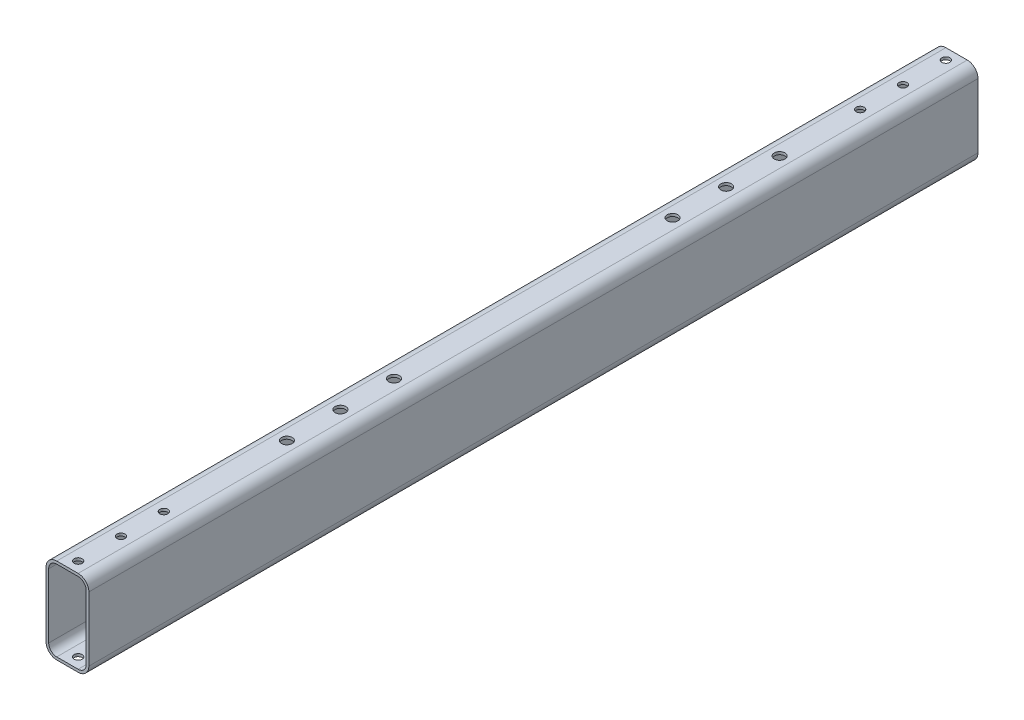
SolidWorks part; units mm, degrees
material "6061-T6 (SS)"
ref_plane "Front Plane" through (0, 0, 0) normal (0, 0, 1) x (1, 0, 0)
ref_plane "Top Plane" through (0, 0, 0) normal (0, 1, 0) x (1, 0, 0)
ref_plane "Right Plane" through (0, 0, 0) normal (1, 0, 0) x (0, 0, -1)
sketch "Sketch1" plane through (0, 0, 0) normal (0, 0, 1) x (1, 0, 0)
  line L1 (-6.35, -25.4) -> (6.35, -25.4)
  line L2 (-12.7, -19.05) -> (-12.7, 19.05)
  line L3 (-6.35, 25.4) -> (6.35, 25.4)
  line L4 (12.7, -19.05) -> (12.7, 19.05)
  line L5 (-12.7, -25.4) -> (12.7, 25.4) construction
  line L6 (-12.7, 25.4) -> (12.7, -25.4) construction
  arc A0 (-12.7, -19.05) -> (-6.35, -25.4) centre (-6.35, -19.05) ccw
  arc A1 (6.35, -25.4) -> (12.7, -19.05) centre (6.35, -19.05) ccw
  arc A2 (6.35, 25.4) -> (12.7, 19.05) centre (6.35, 19.05) cw
  arc A3 (-12.7, 19.05) -> (-6.35, 25.4) centre (-6.35, 19.05) cw
  point P0 (0, 0)
  dimension "D3" = 6.35
  dimension "D1" = 50.8
  dimension "D2" = 25.4
extrude "Extrude-Thin1" add sketch "Sketch1" along normal blind 527.05 thin thin type one direction reverse wall 1.5875
hole_wizard "3/16 (0.1875) Diameter Hole1" positions "3DSketch1" profile "Sketch3" hole size "3/16" standard "ANSI Inch" end condition through all
sketch3d "3DSketch1"
  line L1 (6.35, 25.4, 0) -> (-6.35, 25.4, 0) construction
  line L6 (0, 25.4, 527.05) -> (0, 25.4, 0) construction
  line L7 (6.35, 25.4, 527.05) -> (-6.35, 25.4, 527.05) construction
  point P57 (0, 25.4, 6.35)
  point P59 (0, 25.4, 31.75)
  point P61 (0, 25.4, 57.15)
  point P63 (0, 25.4, 495.3)
  point P65 (0, 25.4, 469.9)
  point P67 (0, 25.4, 520.7)
  dimension "D1" = 25.4
  dimension "D2" = 25.4
  dimension "D3" = 6.35
  dimension "D4" = 25.4
  dimension "D5" = 25.4
  dimension "D6" = 6.35
sketch "Sketch3" plane through (0, 25.4, 520.7) normal (1, 0, 0) x (0, 0, 1)
  line L0 (0, 0) -> (0, 50.8)
  line L1 (0, 50.8) -> (2.3812, 50.8)
  line L2 (2.3812, 50.8) -> (2.3812, 0)
  line L5 (2.3812, 0) -> (0, 0)
  line L11 (0, -6.35) -> (0, 107.95) construction
  dimension "Thru Hole Dia." = 4.7625
  dimension "Thru Hole Depth" = 50.8
hole_wizard "3/16 (0.195) Diameter Hole1" positions "Sketch4" profile "Sketch5" hole size "3/16" standard "ANSI Inch" end condition up to next
sketch "Sketch4" plane through (0, -25.4, 0) normal (0, -1, 0) x (-1, 0, 0)
  point P28 (3.175, -85.725)
  point P31 (-3.175, -111.125)
  point P34 (3.175, -136.525)
  point P37 (-3.175, -161.925)
  point P40 (3.175, -187.325)
  point P43 (3.175, -339.725)
  point P46 (-3.175, -365.125)
  point P49 (3.175, -390.525)
  point P52 (-3.175, -415.925)
  point P60 (-3.175, -212.725)
  point P63 (3.175, -238.125)
  point P66 (-3.175, -263.525)
  point P69 (3.175, -288.925)
  point P72 (-3.175, -314.325)
sketch "Sketch5" plane through (-3.175, -25.4, 85.725) normal (1, 0, 0) x (0, 0, -1)
  line L0 (0, 0) -> (0, 1.5875)
  line L1 (0, 1.5875) -> (2.4765, 1.5875)
  line L2 (2.4765, 1.5875) -> (2.4765, 0)
  line L5 (2.4765, 0) -> (0, 0)
  line L11 (0, -6.35) -> (0, 107.95) construction
  dimension "Thru Hole Dia." = 4.953
  dimension "Thru Hole Depth" = 1.5875
hole_wizard "1/4 (0.25) Diameter Hole1" positions "Sketch7" profile "Sketch6" hole size "1/4" standard "ANSI Inch"
sketch "Sketch7" plane through (0, 25.4, 0) normal (0, 1, 0) x (1, 0, 0)
  point P0 (0, -104.85)
  point P3 (0, -136.6)
  point P6 (0, -168.35)
  point P9 (0, -396.9748)
  point P12 (0, -365.2248)
  point P15 (0, -333.4748)
sketch "Sketch6" plane through (0, 25.4, 104.85) normal (1, 0, 0) x (0, 0, 1)
  line L0 (0, 0) -> (0, 27.3077)
  line L1 (0, 27.3077) -> (3.175, 25.4)
  line L2 (3.175, 25.4) -> (3.175, 0)
  line L5 (3.175, 0) -> (0, 0)
  line L10 (0, 27.3077) -> (-3.175, 25.4) construction
  line L11 (0, -6.35) -> (0, 107.95) construction
  dimension "Hole Dia." = 6.35
  dimension "Hole Depth" = 25.4
  dimension "Drill Angle" = 118
